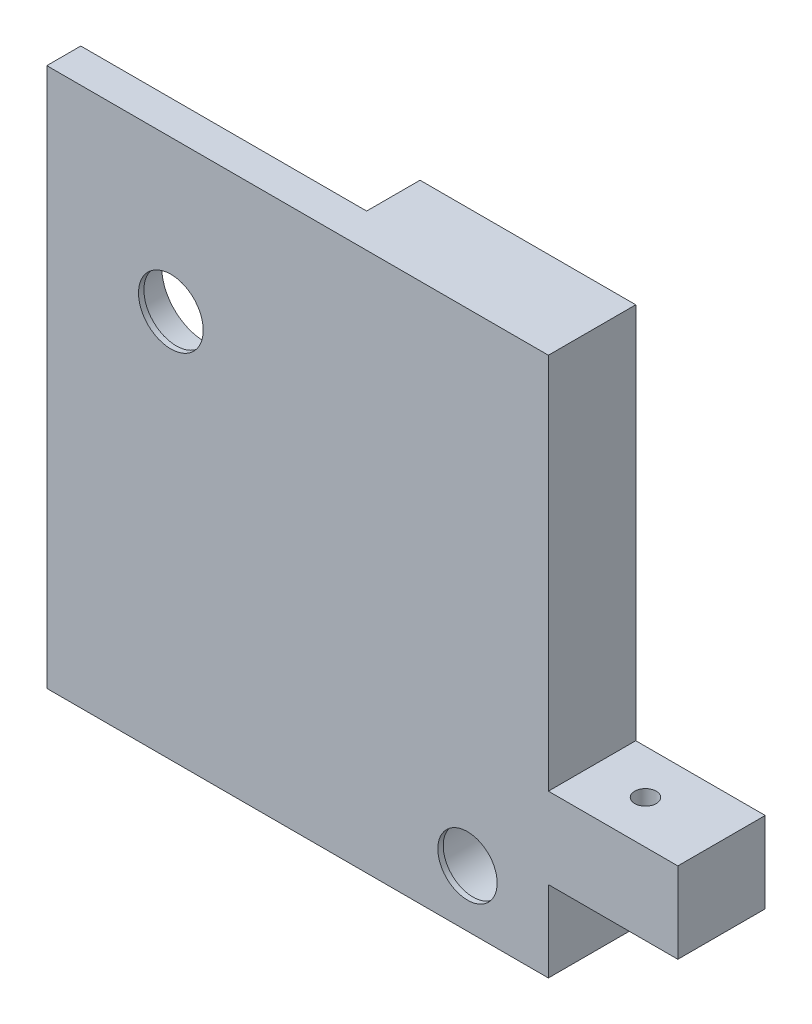
SolidWorks part; units mm, degrees
ref_plane "Front Plane" through (0, 0, 0) normal (0, 0, 1) x (1, 0, 0)
ref_plane "Top Plane" through (0, 0, 0) normal (0, 1, 0) x (1, 0, 0)
ref_plane "Right Plane" through (0, 0, 0) normal (1, 0, 0) x (0, 0, -1)
sketch "Sketch1" plane through (0, 0, 0) normal (0, 0, 1) x (1, 0, 0)
  line L1 (-76.1871, 64.9281) -> (16.8129, 64.9281)
  line L2 (-76.1871, 64.9281) -> (-76.1871, -35.0719)
  line L3 (-76.1871, -35.0719) -> (16.8129, -35.0719)
  line L4 (16.8129, 64.9281) -> (16.8129, -35.0719)
  dimension "D1" = 93
  dimension "D2" = 100
extrude "Boss-Extrude2" add sketch "Sketch1" along normal blind 6.3 contours L1 L4 L3 L2
sketch "Sketch3" plane through (0, 0, 0) normal (0, 0, -1) x (-1, 0, 0)
  line L0 (76.1871, -35.0719) -> (-16.8129, -35.0719) construction
  line L1 (-16.8129, 64.9281) -> (23.1871, 64.9281)
  line L2 (-16.8129, 64.9281) -> (-16.8129, -35.0719)
  line L3 (-16.8129, -35.0719) -> (23.1871, -35.0719)
  line L4 (23.1871, 64.9281) -> (23.1871, -35.0719)
  line L5 (-16.8129, 64.9281) -> (-16.8129, -35.0719) construction
  dimension "D1" = 0
  dimension "D2" = 0
  dimension "D3" = 40
  dimension "D4" = 100
extrude "Boss-Extrude3" add sketch "Sketch3" along normal blind 9.9
sketch "Sketch4" plane through (16.8129, 0, 0) normal (1, 0, 0) x (0, 0, -1)
  line L0 (-6.3, 64.9281) -> (-6.3, -35.0719) construction
  line L1 (-6.3, -5.0719) -> (9.9, -5.0719)
  line L2 (-6.3, -5.0719) -> (-6.3, -20.0719)
  line L3 (-6.3, -20.0719) -> (9.9, -20.0719)
  line L4 (9.9, -5.0719) -> (9.9, -20.0719)
  line L5 (9.9, 64.9281) -> (9.9, -35.0719) construction
  line L6 (-6.3, -35.0719) -> (9.9, -35.0719) construction
  dimension "D1" = 15
  dimension "D2" = 15
extrude "Boss-Extrude4" add sketch "Sketch4" along normal blind 24
sketch "Sketch5" plane through (0, -5.0719, 0) normal (0, 1, 0) x (1, 0, 0)
  line L0 (40.8129, -6.3) -> (16.8129, -6.3) construction
  line L2 (16.8129, 9.9) -> (16.8129, -6.3) construction
  circle A0 centre (26.8129, 1.7) radius 2
  dimension "D2" = 4
  dimension "D3" = 10
  dimension "D1" = 8
extrude "Cut-Extrude1" cut sketch "Sketch5" against normal blind 50
sketch "Sketch6" plane through (0, 0, -9.9) normal (0, 0, -1) x (-1, 0, 0)
  line L0 (-16.8129, -35.0719) -> (23.1871, -35.0719) construction
  line L1 (-16.8129, -20.0719) -> (-16.8129, -35.0719) construction
  circle A0 centre (-1.8129, -24.5719) radius 7.5
  dimension "D1" = 15
  dimension "D2" = 10.5
  dimension "D3" = 15
extrude "Cut-Extrude2" cut sketch "Sketch6" against normal blind 50
sketch "Sketch7" plane through (0, 0, 0) normal (0, 0, -1) x (-1, 0, 0)
  line L0 (76.1871, -35.0719) -> (23.1871, -35.0719) construction
  line L2 (-16.8129, 64.9281) -> (-16.8129, -5.0719) construction
  circle A0 centre (53.1871, 36.9281) radius 8
  dimension "D1" = 16
  dimension "D2" = 72
  dimension "D3" = 70
extrude "Cut-Extrude3" cut sketch "Sketch7" against normal blind 50
extrude "Extrude-Thin1" add sketch "Sketch7<2>" along normal blind 1 from surface thin starting at face at (-45.1871, 36.9281, 6.3) thin type one direction reverse wall 2
sketch "Sketch7<2>" plane through (0, 0, 0) normal (0, 0, -1) x (-1, 0, 0) same geometry as "Sketch7"
extrude "Extrude-Thin2" add sketch "Sketch6<2>" along normal blind 1 from surface thin starting at face at (9.3129, -24.5719, 6.3) thin type one direction reverse wall 2
sketch "Sketch6<2>" plane through (0, 0, -9.9) normal (0, 0, -1) x (-1, 0, 0) same geometry as "Sketch6"
